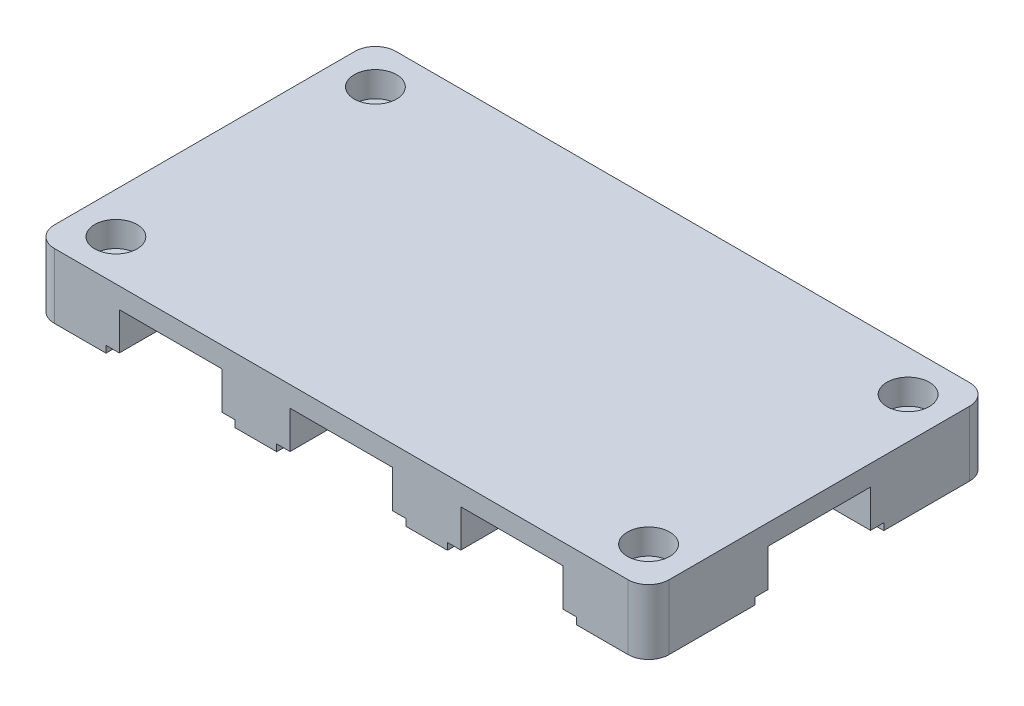
SolidWorks part; units mm, degrees
ref_plane "前视基准面" through (0, 0, 0) normal (0, 0, 1) x (1, 0, 0)
ref_plane "上视基准面" through (0, 0, 0) normal (0, 1, 0) x (1, 0, 0)
ref_plane "右视基准面" through (0, 0, 0) normal (1, 0, 0) x (0, 0, -1)
other "Configuration Table"
sketch "草图1" plane through (0, 0, 0) normal (0, 1, 0) x (1, 0, 0)
  line L1 (-42, -25) -> (42, -25)
  line L2 (-45, -22) -> (-45, 22)
  line L3 (-42, 25) -> (42, 25)
  line L4 (45, -22) -> (45, 22)
  line L5 (-45, -25) -> (45, 25) construction
  line L6 (-45, 25) -> (45, -25) construction
  arc A0 (-42, -25) -> (-45, -22) centre (-42, -22) cw
  arc A1 (45, -22) -> (42, -25) centre (42, -22) cw
  arc A2 (45, 22) -> (42, 25) centre (42, 22) ccw
  arc A3 (-45, 22) -> (-42, 25) centre (-42, 22) cw
  circle A4 centre (-39, 19) radius 1.6
  circle A5 centre (39, 19) radius 1.6
  circle A6 centre (-39, -19) radius 1.6
  circle A7 centre (39, -19) radius 1.6
  point P0 (0, 0)
  dimension "D3" = 3
  dimension "D4" = 3.2
  dimension "D1" = 90
  dimension "D2" = 50
  dimension "D5" = 6
  dimension "D6" = 6
  dimension "D7" = 6
  dimension "D8" = 6
extrude "凸台-拉伸1" add sketch "草图1" along normal blind 8.5
sketch "草图2" plane through (0, 8.5, 0) normal (0, 1, 0) x (1, 0, 0)
  line L0 (0, 31.0621) -> (0, -32.1848) construction
  line L1 (-42, -25) -> (42, -25) construction
  line L2 (-7.5, -14.7) -> (7.5, -14.7)
  line L3 (-7.5, -14.7) -> (-7.5, -25)
  line L4 (-7.5, -25) -> (7.5, -25)
  line L5 (7.5, -14.7) -> (7.5, -25)
  line L6 (-25, 35.1788) -> (-25, -33.1205) construction
  line L7 (0, 0) -> (-45, 0) construction
  line L8 (-45, 22) -> (-45, -22) construction
  line L9 (0, 0) -> (45, 0) construction
  line L10 (-32.5, -14.7) -> (-17.5, -14.7)
  line L11 (-32.5, -14.7) -> (-32.5, -25)
  line L12 (-32.5, -25) -> (-17.5, -25)
  line L13 (-17.5, -14.7) -> (-17.5, -25)
  line L14 (45, -22) -> (45, 22) construction
  line L15 (25, 31.9977) -> (25, -37.05) construction
  line L17 (17.5, -14.7) -> (32.5, -14.7)
  line L18 (17.5, -14.7) -> (17.5, -25)
  line L19 (17.5, -25) -> (32.5, -25)
  line L20 (32.5, -14.7) -> (32.5, -25)
  line L21 (-45, 7.5) -> (-34.7, 7.5)
  line L22 (-45, 7.5) -> (-45, -7.5)
  line L23 (-45, -7.5) -> (-34.7, -7.5)
  line L24 (-34.7, 7.5) -> (-34.7, -7.5)
  line L25 (45, 7.5) -> (34.7, 7.5)
  line L26 (45, 7.5) -> (45, -7.5)
  line L27 (45, -7.5) -> (34.7, -7.5)
  line L28 (34.7, 7.5) -> (34.7, -7.5)
  point P9 (0, -14.7)
  point P21 (-25, -14.7)
  point P32 (25, -14.7)
  point P41 (-34.7, 0)
  point P42 (34.7, 0)
  dimension "D1" = 15
  dimension "D2" = 10.3
  dimension "D3" = 20
  dimension "D4" = 70
sketch "草图3" plane through (0, 8.5, 0) normal (0, 1, 0) x (1, 0, 0)
  line L0 (42, 25) -> (-42, 25) construction
  line L1 (-13.742, 25) -> (-4.542, 25)
  line L2 (-13.742, 25) -> (-13.742, 17.4)
  line L3 (-13.742, 17.4) -> (-4.542, 17.4)
  line L4 (-4.542, 25) -> (-4.542, 17.4)
  line L5 (-9.142, 32.9169) -> (-9.142, 4.8795) construction
  line L6 (-45, 22) -> (-45, -22) construction
  point P10 (-9.142, 17.4)
  dimension "D1" = 9.2
  dimension "D2" = 7.6
  dimension "D3" = 35.858
sketch "草图4" plane through (0, 8.5, 0) normal (0, 1, 0) x (1, 0, 0)
  line L0 (6.466, 34.8045) -> (6.466, -37.05) construction
  line L1 (-45, 22) -> (-45, -22) construction
  line L2 (42, 25) -> (-42, 25) construction
  line L3 (2.466, 25) -> (10.466, 25)
  line L4 (2.466, 25) -> (2.466, 19)
  line L5 (2.466, 19) -> (10.466, 19)
  line L6 (10.466, 25) -> (10.466, 19)
  point P10 (6.466, 19)
  dimension "D1" = 51.466
  dimension "D2" = 6
  dimension "D3" = 8
sketch "草图7" plane through (0, 8.5, 0) normal (0, 1, 0) x (1, 0, 0)
  line L0 (-25, 40.2318) -> (-25, -33.5875) construction
  line L1 (-29.8, 21.9) -> (-20.2, 21.9)
  line L2 (-29.8, 21.9) -> (-29.8, 33)
  line L3 (-29.8, 33) -> (-20.2, 33)
  line L4 (-20.2, 21.9) -> (-20.2, 33)
  line L5 (-45, 22) -> (-45, -22) construction
  line L6 (42, 25) -> (-42, 25) construction
  point P8 (-25, 21.9)
  dimension "D1" = 20
  dimension "D2" = 9.6
  dimension "D3" = 3.1
  dimension "D4" = 11.1
extrude "切除-拉伸1" cut sketch "草图2" along normal blind 6.5 from surface starting at face at (-39, 0, 20.6)
extrude "切除-拉伸2" cut sketch "草图3" along normal blind 3.4 from surface starting at face at (0, 0, 8.5071)
extrude "切除-拉伸3" cut sketch "草图4" along normal blind 2.6 from surface starting at face at (-1.1427, 0, 4.7938)
extrude "切除-拉伸4" cut sketch "草图7" along normal blind 1 from surface starting at face at (-0.2973, 0, 1.8167)
sketch "草图8" plane through (0, 0, 0) normal (0, -1, 0) x (1, 0, 0)
  line L0 (-25, 33.8928) -> (-25, -41.0205) construction
  line L1 (-33.2, -9.45) -> (-45, -9.45)
  line L2 (-33.2, -9.45) -> (-33.2, 9.45)
  line L3 (-33.2, 9.45) -> (-45, 9.45)
  line L4 (-45, -9.45) -> (-45, 9.45)
  line L7 (-31.5, -1) -> (-27.3, -1)
  line L8 (-31.5, -1) -> (-31.5, 1)
  line L9 (-31.5, 1) -> (-27.3, 1)
  line L10 (-27.3, -1) -> (-27.3, 1)
  line L11 (-29.15, -20.5) -> (-20.85, -20.5)
  line L12 (-29.15, -20.5) -> (-29.15, -21.9)
  line L13 (-29.15, -21.9) -> (-20.85, -21.9)
  line L14 (-20.85, -20.5) -> (-20.85, -21.9)
  line L15 (-17.66, -19.4) -> (-16.46, -19.4)
  line L16 (-17.66, -19.4) -> (-17.66, -17.4)
  line L17 (-17.66, -17.4) -> (-16.46, -17.4)
  line L18 (-16.46, -19.4) -> (-16.46, -17.4)
  line L19 (-0.712, -19.4) -> (-1.912, -19.4)
  line L20 (-0.712, -19.4) -> (-0.712, -17.4)
  line L21 (-0.712, -17.4) -> (-1.912, -17.4)
  line L22 (-1.912, -19.4) -> (-1.912, -17.4)
  line L23 (4.766, -19) -> (8.166, -19)
  line L24 (4.766, -19) -> (4.766, -17.6)
  line L25 (4.766, -17.6) -> (8.166, -17.6)
  line L26 (8.166, -19) -> (8.166, -17.6)
  line L27 (18.85, -19.3) -> (31.15, -19.3)
  line L28 (18.85, -19.3) -> (18.85, -25)
  line L29 (18.85, -25) -> (31.15, -25)
  line L30 (31.15, -19.3) -> (31.15, -25)
  line L31 (-45, 7.5) -> (-45, 22) construction
  line L32 (-17.5, 25) -> (-32.5, 25) construction
  line L33 (20, -6.4) -> (34.7, -6.4)
  line L34 (20, -6.4) -> (20, 6.4)
  line L35 (20, 6.4) -> (34.7, 6.4)
  line L36 (34.7, -6.4) -> (34.7, 6.4)
  line L37 (33.2, -9.45) -> (45, -9.45)
  line L38 (33.2, -9.45) -> (33.2, 9.45)
  line L39 (33.2, 9.45) -> (45, 9.45)
  line L40 (45, -9.45) -> (45, 9.45)
  line L41 (25, 37.9856) -> (25, 9.6) construction
  line L42 (7.5, 25) -> (17.5, 25) construction
  line L43 (-34.45, 13.2) -> (-15.55, 13.2)
  line L44 (-34.45, 13.2) -> (-34.45, 25)
  line L45 (-34.45, 25) -> (-15.55, 25)
  line L46 (-15.55, 13.2) -> (-15.55, 25)
  line L49 (-9.45, 13.2) -> (9.45, 13.2)
  line L50 (-9.45, 13.2) -> (-9.45, 25)
  line L51 (-9.45, 25) -> (9.45, 25)
  line L52 (9.45, 13.2) -> (9.45, 25)
  line L54 (15.55, 13.2) -> (34.45, 13.2)
  line L55 (15.55, 13.2) -> (15.55, 25)
  line L56 (15.55, 25) -> (34.45, 25)
  line L57 (34.45, 13.2) -> (34.45, 25)
  point P6 (-25, 13.2)
  point P25 (25, 13.2)
  dimension "D1" = 18.9
  dimension "D2" = 20
  dimension "D3" = 11.8
  dimension "D4" = 70
extrude "切除-拉伸5" cut sketch "草图8" against normal blind 3.4 contours L27 L30 L29 L28
extrude "切除-拉伸6" cut sketch "草图8<3>" against normal blind 2 contours L33 L36 L35 L34
sketch "草图8<3>" plane through (0, 0, 0) normal (0, -1, 0) x (1, 0, 0) same geometry as "草图8"
extrude "切除-拉伸7" cut sketch "草图8<4>" against normal blind 1 contours L39 L40 L37 L38 | L25 L26 L23 L24 | L22 L21 L20 L19 | L16 L17 L18 L15 | L11 L14 L13 L12 | L9 L10 L7 L8 | L2 L3 L4 L1 | L43 L46 L45 L44 | L49 L52 L51 L50 | L54 L57 L56 L55
sketch "草图8<4>" plane through (0, 0, 0) normal (0, -1, 0) x (1, 0, 0) same geometry as "草图8"
sketch "草图9" plane through (0, 8.5, 0) normal (0, 1, 0) x (1, 0, 0)
  circle A0 centre (-39, 19) radius 3.1
  circle A1 centre (-39, -19) radius 3.1
  circle A2 centre (39, 19) radius 3.1
  circle A3 centre (39, -19) radius 3.1
  dimension "D1" = 6.2
extrude "切除-拉伸8" cut sketch "草图9" against normal blind 2.7 contours A0 | A1 | A3 | A2
sketch "草图10" plane through (0, 8.5, 0) normal (0, 1, 0) x (1, 0, 0)
  line L4 (-42, -25) -> (42, -25)
  line L5 (45, -22) -> (45, 22)
  line L6 (42, 25) -> (-42, 25)
  line L7 (-45, 22) -> (-45, -22)
  line L8 (-42, -25) -> (42, -25)
  line L9 (45, -22) -> (45, 22)
  line L10 (42, 25) -> (-42, 25)
  line L11 (-45, 22) -> (-45, -22)
  circle A0 centre (39, 19) radius 3.1 construction
  circle A1 centre (39, -19) radius 3.1
  circle A2 centre (39, -19) radius 3.1
  circle A3 centre (-39, -19) radius 3.1 construction
  circle A4 centre (-39, 19) radius 3.1 construction
  circle A5 centre (39, 19) radius 3.1
  circle A6 centre (-39, -19) radius 3.1
  circle A7 centre (-39, 19) radius 3.1
  arc A12 (-45, -22) -> (-42, -25) centre (-42, -22) ccw
  arc A13 (42, -25) -> (45, -22) centre (42, -22) ccw
  arc A14 (45, 22) -> (42, 25) centre (42, 22) ccw
  arc A15 (-42, 25) -> (-45, 22) centre (-42, 22) ccw
  arc A16 (-45, -22) -> (-42, -25) centre (-42, -22) ccw
  arc A17 (42, -25) -> (45, -22) centre (42, -22) ccw
  arc A18 (45, 22) -> (42, 25) centre (42, 22) ccw
  arc A19 (-42, 25) -> (-45, 22) centre (-42, 22) ccw
  dimension "D1" = 0
  dimension "D2" = 0
extrude "凸台-拉伸2" add sketch "草图10" along normal blind 1
